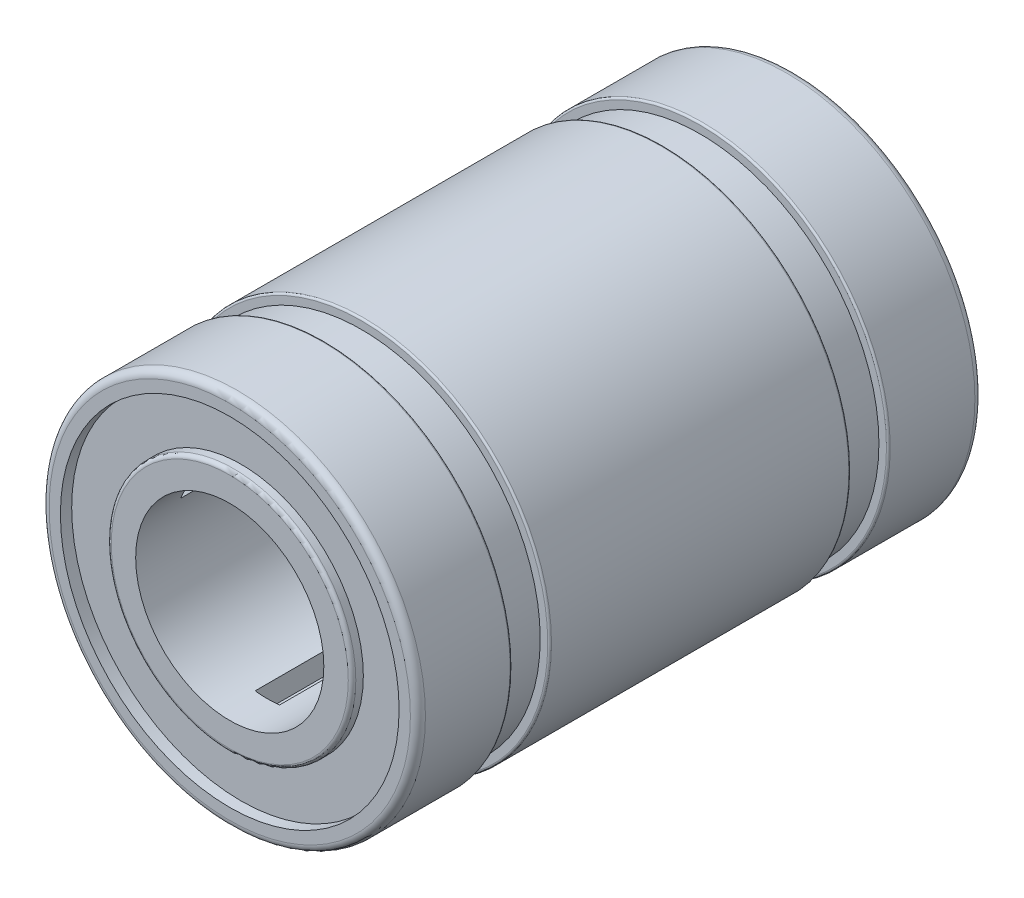
SolidWorks part; units mm, degrees
ref_plane "Front Plane" through (0, 0, 0) normal (0, 0, 1) x (1, 0, 0)
ref_plane "Top Plane" through (0, 0, 0) normal (0, 1, 0) x (1, 0, 0)
ref_plane "Right Plane" through (0, 0, 0) normal (1, 0, 0) x (0, 0, -1)
sketch "Sketch1" plane through (0, 0, 0) normal (0, 0, 1) x (1, 0, 0)
  circle A0 centre (0, 0) radius 5
  dimension "D1" = 10
extrude "Boss-Extrude1" add sketch "Sketch1" along normal blind 4 and the other way blind 4
sketch "Sketch2" plane through (0, 0, 4) normal (0, 0, 1) x (1, 0, 0)
  circle A0 centre (0, 0) radius 4.75
  dimension "D1" = 9.5
extrude "Boss-Extrude2" add sketch "Sketch2" along normal blind 1 and the other way blind 9
sketch "Sketch3" plane through (0, 0, 5) normal (0, 0, 1) x (1, 0, 0)
  circle A0 centre (0, 0) radius 5
extrude "Boss-Extrude3" add sketch "Sketch3" along normal blind 2.5
sketch "Sketch4" plane through (0, 0, -5) normal (0, 0, -1) x (-1, 0, 0)
  circle A0 centre (0, 0) radius 5
extrude "Boss-Extrude4" add sketch "Sketch4" along normal blind 2.5
sketch "Sketch5" plane through (0, 0, 7.5) normal (0, 0, 1) x (1, 0, 0)
  circle A0 centre (0, 0) radius 4.5
  dimension "D1" = 9
extrude "Cut-Extrude1" cut sketch "Sketch5" against normal blind 0.3
sketch "Sketch6" plane through (0, 0, -7.5) normal (0, 0, -1) x (-1, 0, 0)
  circle A0 centre (0, 0) radius 4.5
  dimension "D1" = 9
extrude "Cut-Extrude2" cut sketch "Sketch6" against normal blind 0.3
sketch "Sketch7" plane through (0, 0, -7.2) normal (0, 0, -1) x (-1, 0, 0)
  circle A0 centre (0, 0) radius 3.25
  dimension "D1" = 6.5
extrude "Boss-Extrude5" add sketch "Sketch7" along normal blind 0.3
sketch "Sketch8" plane through (0, 0, 7.2) normal (0, 0, 1) x (1, 0, 0)
  circle A0 centre (0, 0) radius 3.25
  dimension "D1" = 6.5
extrude "Boss-Extrude6" add sketch "Sketch8" along normal blind 0.3
sketch "Sketch9" plane through (0, 0, -7.5) normal (0, 0, -1) x (-1, 0, 0)
  circle A0 centre (0, 0) radius 2.5
  dimension "D1" = 5
extrude "Cut-Extrude3" cut sketch "Sketch9" against normal blind 20.3
sketch "Sketch10" plane through (0, 0, -7.5) normal (0, 0, -1) x (-1, 0, 0)
  line L0 (-1.5135, 1.249) -> (-2.8167, 1.251) construction
  line L1 (-0.3249, -1.9352) -> (0.3249, -1.9352)
  line L2 (-0.3249, -1.9352) -> (-0.3249, -3.0648)
  line L3 (-0.3249, -3.0648) -> (0.3249, -3.0648)
  line L4 (0.3249, -1.9352) -> (0.3249, -3.0648)
  line L5 (-0.3249, -1.9352) -> (0.3249, -3.0648) construction
  line L6 (-0.3249, -3.0648) -> (0.3249, -1.9352) construction
  line L7 (-2.4917, 1.8138) -> (-1.8384, 0.6862) construction
  line L8 (-1.5135, 1.249) -> (-2.4917, 1.8138)
  line L9 (-1.5135, 1.249) -> (-1.8384, 0.6862)
  line L10 (-1.8384, 0.6862) -> (-2.8167, 1.251)
  line L11 (-2.4917, 1.8138) -> (-2.8167, 1.251)
  line L12 (1.8384, 0.6862) -> (2.4917, 1.8138) construction
  line L13 (2.8167, 1.251) -> (1.5135, 1.249) construction
  line L14 (1.8384, 0.6862) -> (2.8167, 1.251)
  line L15 (1.8384, 0.6862) -> (1.5135, 1.249)
  line L16 (1.5135, 1.249) -> (2.4917, 1.8138)
  line L17 (2.8167, 1.251) -> (2.4917, 1.8138)
  circle A0 centre (0, 0) radius 2.5 construction
  point P0 (0, -2.5)
  point P10 (-2.1651, 1.25)
  point P15 (2.1651, 1.25)
  point P20 (0, 0)
  dimension "D1" = 3
extrude "Cut-Extrude4" cut sketch "Sketch10" against normal blind 14
sketch "Sketch11" plane through (0, 0, -7.5) normal (0, 0, -1) x (-1, 0, 0)
  circle A0 centre (0, 0) radius 2.5
  circle A1 centre (0, 0) radius 3.25
  dimension "D1" = 0.75
extrude "Boss-Extrude7" add sketch "Sketch11" against normal blind 1
fillet "Fillet1" radius 0.2 2 edges at (5, 0, 7.5) (-5, 0, -7.5)
fillet "Fillet2" radius 0.05 4 edges at (5, 0, 5) (5, 0, 4) (5, 0, -4) (-5, 0, -5)
fillet "Fillet3" radius 0.1 2 edges at (3.25, 0, 7.5) (-3.25, 0, -7.5)
